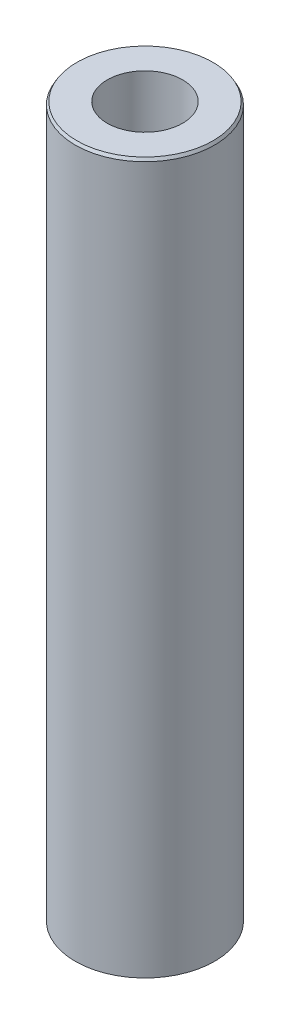
SolidWorks part; units mm, degrees
ref_plane "Front Plane" through (0, 0, 0) normal (0, 0, 1) x (1, 0, 0)
ref_plane "Top Plane" through (0, 0, 0) normal (0, 1, 0) x (1, 0, 0)
ref_plane "Right Plane" through (0, 0, 0) normal (1, 0, 0) x (0, 0, -1)
sketch "Sketch1" plane through (0, 0, 0) normal (0, 1, 0) x (1, 0, 0)
  circle A0 centre (0, 0) radius 42.5
  dimension "SHAFT_OD" = 85
extrude "Boss-Extrude1" add sketch "Sketch1" along normal blind 433.9009
sketch "Sketch2" plane through (0, 0, 0) normal (0, 1, 0) x (1, 0, 0)
  circle A0 centre (0, 0) radius 22.9743
  dimension "BORE_D" = 45.9485
extrude "Cut-Extrude1" cut sketch "Sketch2" along normal through all
chamfer "Chamfer1" distance 1.7572 angle 30 2 edges at (0, 433.9009, 42.5) (0, 0, 42.5) first distance on face at (0, 433.9009, 42.5) first distance on face at (0, 0, 22.9743)
